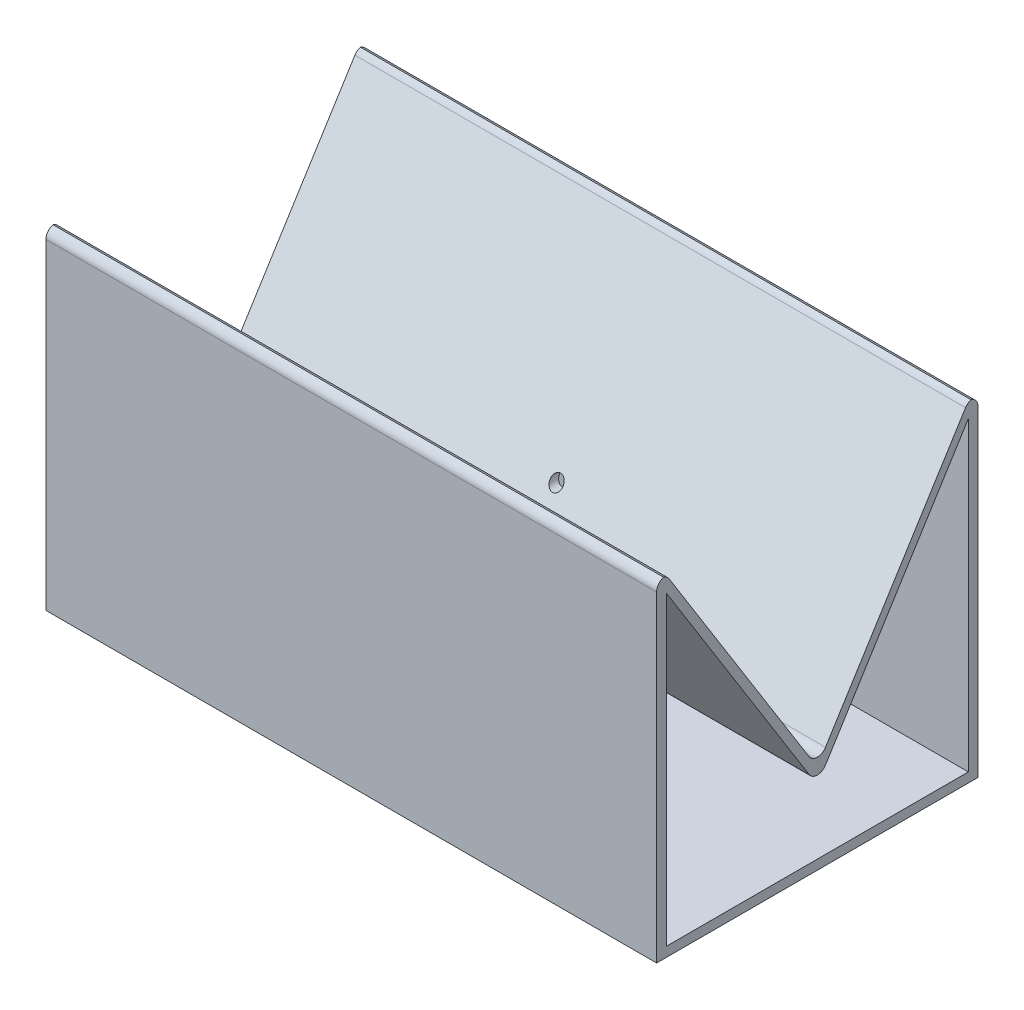
SolidWorks part; units mm, degrees
ref_plane "Front Plane" through (0, 0, 0) normal (0, 0, 1) x (1, 0, 0)
ref_plane "Top Plane" through (0, 0, 0) normal (0, 1, 0) x (1, 0, 0)
ref_plane "Right Plane" through (0, 0, 0) normal (1, 0, 0) x (0, 0, -1)
sketch "Sketch1" plane through (0, 0, 0) normal (0, 1, 0) x (1, 0, 0)
  line L1 (-95, -50) -> (95, -50)
  line L2 (-95, -50) -> (-95, 50)
  line L3 (-95, 50) -> (95, 50)
  line L4 (95, -50) -> (95, 50)
  line L5 (-95, -50) -> (95, 50) construction
  line L6 (-95, 50) -> (95, -50) construction
  point P0 (0, 0)
  dimension "D1" = 190
  dimension "D2" = 100
extrude "Boss-Extrude1" add sketch "Sketch1" along normal blind 3
ref_plane "Plane1" through (0, 0, 0) normal (1, 0, 0) x (0, 0, -1)
sketch "Sketch2" plane through (0, 0, 0) normal (1, 0, 0) x (0, 0, -1)
  line L0 (-50, 3) -> (-50, 103) construction
  line L1 (0, 3) -> (0, 103) construction
  line L2 (-50, 3) -> (50, 3) construction
  line L3 (50, 3) -> (50, 103) construction
  line L4 (50, 103) -> (47, 103)
  line L5 (-50, 3) -> (-47, 3)
  line L6 (-50, 3) -> (-50, 103)
  line L7 (-50, 103) -> (-47, 103)
  line L8 (-47, 3) -> (-47, 103)
  line L9 (47, 3) -> (47, 103)
  line L10 (50, 3) -> (47, 3)
  line L11 (50, 3) -> (50, 103)
  line L12 (-50, 23) -> (50, 23) construction
  line L13 (-47, 98.2) -> (0, 23)
  line L14 (-47, 103) -> (0, 27.8)
  line L15 (0, 27.8) -> (0, 23)
  line L16 (47, 98.2) -> (0, 23)
  line L17 (47, 103) -> (0, 27.8)
  dimension "D1" = 100
  dimension "D2" = 3
  dimension "D3" = 20
extrude "Boss-Extrude2" add sketch "Sketch2" along normal blind 95 and the other way blind 95 contours L5 L8 L7 L6 | L15 L14 L8 L13 | L9 L17 L15 L16 | L10 L11 L4 L9 region at (0, 53, -48.5) region at (0, 63, -23.5) region at (0, 63, 23.5) region at (0, 53, 48.5)
fillet "Fillet1" radius 3 6 edges at (0, 23, 0) (0, 103, 50) (0, 103, 47) (0, 27.8, 0) (0, 103, -47) (0, 103, -50)
ref_plane "Plane2" through (0, 0, 0) normal (0, 0, 1) x (1, 0, 0)
sketch "Sketch3" plane through (0, 0, 0) normal (0, 0, 1) x (1, 0, 0)
  line L0 (0, 0) -> (0, 102.8825) construction
  line L1 (95, 102.8825) -> (-95, 102.8825) construction
  line L2 (-95, 50) -> (95, 50) construction
  line L3 (-95, 102.8825) -> (95, 102.8825) construction
  line L4 (-95, 102.8825) -> (-95, 0) construction
  line L5 (-95, 0) -> (95, 0) construction
  line L6 (95, 102.8825) -> (95, 0) construction
  circle A0 centre (0, 50) radius 2
  dimension "D2" = 4
  dimension "D1" = 50
extrude "Cut-Extrude1" cut sketch "Sketch3" against normal blind 30 and the other way blind 30
